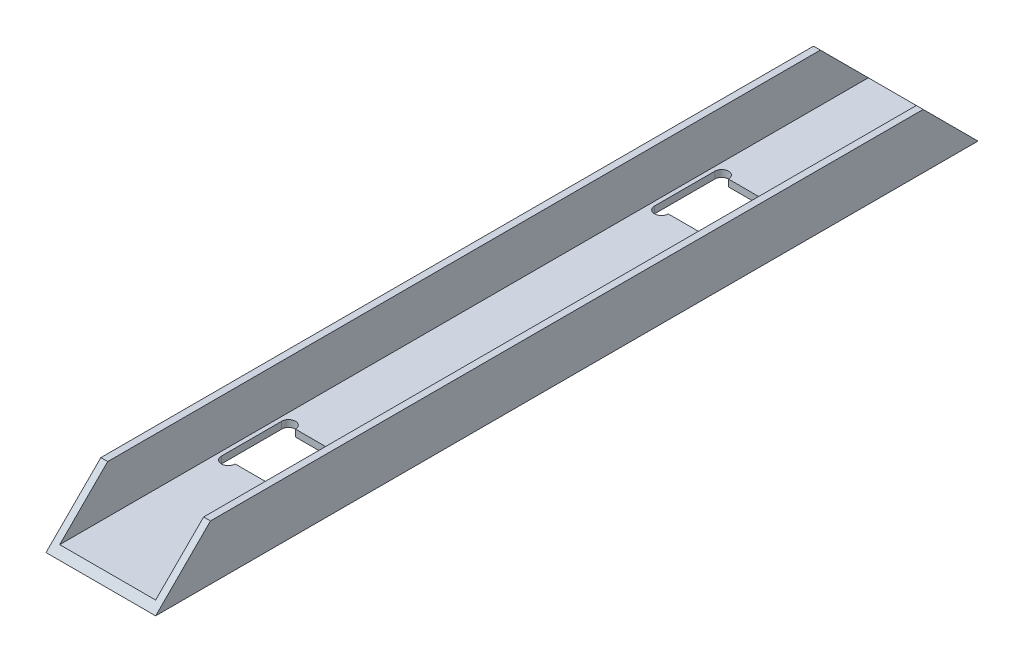
SolidWorks part; units mm, degrees
material "AISI 1010 Steel, hot rolled bar"
ref_plane "Front Plane" through (0, 0, 0) normal (0, 0, 1) x (1, 0, 0)
ref_plane "Top Plane" through (0, 0, 0) normal (0, 1, 0) x (1, 0, 0)
ref_plane "Right Plane" through (0, 0, 0) normal (1, 0, 0) x (0, 0, -1)
sketch "Sketch1" plane through (0, 0, 0) normal (0, 0, 1) x (1, 0, 0)
  line L0 (-25.4, 0) -> (25.4, 0)
  line L1 (25.4, 0) -> (25.4, 25.4)
  line L2 (25.4, 25.4) -> (22.225, 25.4)
  line L3 (22.225, 25.4) -> (22.225, 3.175)
  line L4 (22.225, 3.175) -> (-22.225, 3.175)
  line L5 (-22.225, 3.175) -> (-22.225, 25.4)
  line L6 (-22.225, 25.4) -> (-25.4, 25.4)
  line L7 (-25.4, 25.4) -> (-25.4, 0)
  line L8 (0, 15.5567) -> (0, -9.8218) construction
  dimension "D1" = 3.175
  dimension "D2" = 3.175
  dimension "D3" = 25.4
  dimension "D4" = 50.8
extrude "Boss-Extrude1" add sketch "Sketch1" along normal blind 381
sketch "Sketch2" plane through (25.4, 0, 0) normal (1, 0, 0) x (0, 0, -1)
  line L0 (-381, 0) -> (-355.6, 25.4)
  line L1 (-381, 25.4) -> (0, 25.4) construction
  line L2 (-355.6, 25.4) -> (-381, 25.4)
  line L3 (-381, 25.4) -> (-381, 0)
  line L4 (0, 0) -> (0, 25.4)
  line L5 (0, 25.4) -> (-25.4, 25.4)
  line L6 (-25.4, 25.4) -> (0, 0)
  dimension "D1" = 45
  dimension "D2" = 45
extrude "Cut-Extrude1" cut sketch "Sketch2" against normal through all
sketch "Sketch3" [suppressed] plane through (0, 0, 0) normal (0, -1, 0) x (1, 0, 0)
  line L0 (0, 304.8) -> (0, 0) construction
  line L1 (-25.4, 304.8) -> (25.4, 304.8) construction
  line L2 (-25.4, 0) -> (25.4, 0) construction
  circle A0 centre (0, 254) radius 2.5
  circle A1 centre (0, 76.2) radius 2.5
  dimension "D3" = 5
  dimension "D1" = 177.8
  dimension "D2" = 76.2
extrude "Cut-Extrude2" [suppressed] cut sketch "Sketch3" against normal blind 330.2
sketch "Sketch4" plane through (0, 0, 0) normal (0, -1, 0) x (1, 0, 0)
  line L0 (0, 381) -> (0, 0) construction
  line L1 (-25.4, 381) -> (25.4, 381) construction
  line L2 (-25.4, 190.5) -> (25.4, 190.5) construction
  line L3 (-13.97, 276.86) -> (13.97, 276.86)
  line L4 (-20.32, 276.86) -> (-20.32, 304.8)
  line L5 (-13.97, 304.8) -> (13.97, 304.8)
  line L6 (20.32, 276.86) -> (20.32, 304.8)
  line L7 (-20.32, 276.86) -> (20.32, 304.8) construction
  line L8 (-20.32, 304.8) -> (20.32, 276.86) construction
  line L9 (-25.4, 381) -> (-25.4, 0) construction
  line L10 (25.4, 381) -> (25.4, 0) construction
  line L11 (-20.32, 104.14) -> (-20.32, 76.2)
  line L12 (-13.97, 104.14) -> (13.97, 104.14)
  line L17 (-25.4, 290.83) -> (25.4, 290.83) construction
  line L18 (20.32, 104.14) -> (20.32, 76.2)
  line L19 (-13.97, 76.2) -> (13.97, 76.2)
  arc A0 (-13.97, 304.8) -> (-20.32, 304.8) centre (-17.145, 304.8) ccw
  arc A1 (13.97, 304.8) -> (20.32, 304.8) centre (17.145, 304.8) cw
  arc A2 (13.97, 276.86) -> (20.32, 276.86) centre (17.145, 276.86) ccw
  arc A3 (-13.97, 276.86) -> (-20.32, 276.86) centre (-17.145, 276.86) cw
  arc A4 (-13.97, 76.2) -> (-20.32, 76.2) centre (-17.145, 76.2) cw
  arc A5 (-13.97, 104.14) -> (-20.32, 104.14) centre (-17.145, 104.14) ccw
  arc A6 (13.97, 104.14) -> (20.32, 104.14) centre (17.145, 104.14) cw
  arc A7 (13.97, 76.2) -> (20.32, 76.2) centre (17.145, 76.2) ccw
  point P5 (0, 290.83)
  point P16 (0, 0)
  point P25 (0, 0)
  dimension "D4" = 6.35
  dimension "D1" = 27.94
  dimension "D2" = 40.64
  dimension "D3" = 76.2
extrude "Cut-Extrude3" cut sketch "Sketch4" against normal through all
equation "\"D2@Sketch1\"=\"D1@Sketch1\""
